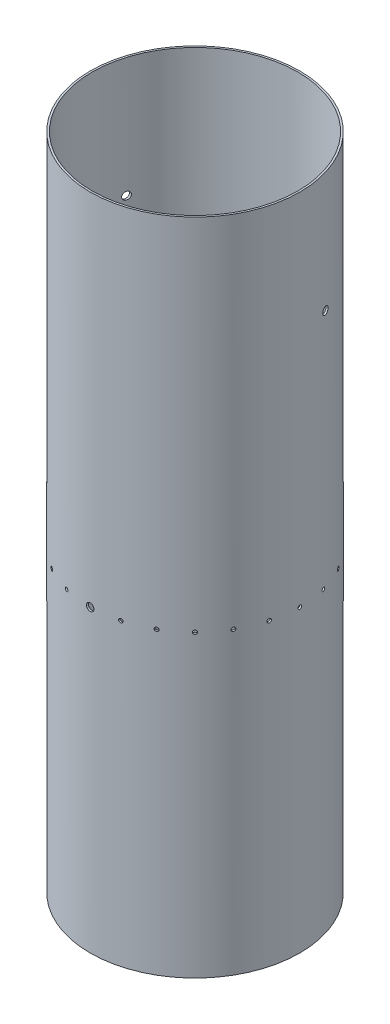
SolidWorks part; units mm, degrees
ref_plane "Front Plane" through (0, 0, 0) normal (0, 0, 1) x (1, 0, 0)
ref_plane "Top Plane" through (0, 0, 0) normal (0, 1, 0) x (1, 0, 0)
ref_plane "Right Plane" through (0, 0, 0) normal (1, 0, 0) x (0, 0, -1)
sketch "Sketch1" plane through (0, 0, 0) normal (0, 1, 0) x (1, 0, 0)
  circle A0 centre (0, 0) radius 88.9
  circle A1 centre (0, 0) radius 87.3125
  dimension "D1" = 177.8
  dimension "D2" = 174.625
extrude "Boss-Extrude1" add sketch "Sketch1" along normal blind 558.8
ref_plane "Plane1" through (0, 0, 88.9) normal (0, 0, 1) x (1, 0, 0)
sketch "Sketch10" plane through (0, 0, 88.9) normal (0, 0, 1) x (1, 0, 0)
  line L0 (88.9, 558.8) -> (-88.9, 558.8) construction
  circle A0 centre (0, 254) radius 1.5875
  dimension "D1" = 3.175
  dimension "D2" = 304.8
extrude "Cut-Extrude1" cut sketch "Sketch10" against normal blind 3.81
ref_axis "Axis1" through (0, 558.8, 0) along (0, -1, 0)
pattern_circular "CirPattern1" count 24 over 360 about axis through (0, 558.8, 0) along (0, -1, 0) of "Cut-Extrude1"
sketch "Sketch12" plane through (0, 0, 88.9) normal (0, 0, 1) x (1, 0, 0)
  circle A0 centre (0, 254) radius 3.175
  dimension "D1" = 6.35
extrude "Cut-Extrude2" cut sketch "Sketch12" against normal through all both and the other way through all
ref_axis "Axis2" through (0, 254, 87.0756) along (0, 0, 1)
sketch "Sketch15" plane through (0, 0, 0) normal (1, 0, 0) x (0, 0, -1)
  line L1 (0, 558.8) -> (0, 0) construction
  circle A2 centre (25.4, 457.2) radius 3.175
  circle A3 centre (0, 254) radius 1.5875 construction
  dimension "D1" = 6.35
  dimension "D3" = 25.4
  dimension "D2" = 203.2
extrude "Cut-Extrude4" cut sketch "Sketch15" against normal through all both and the other way through all
